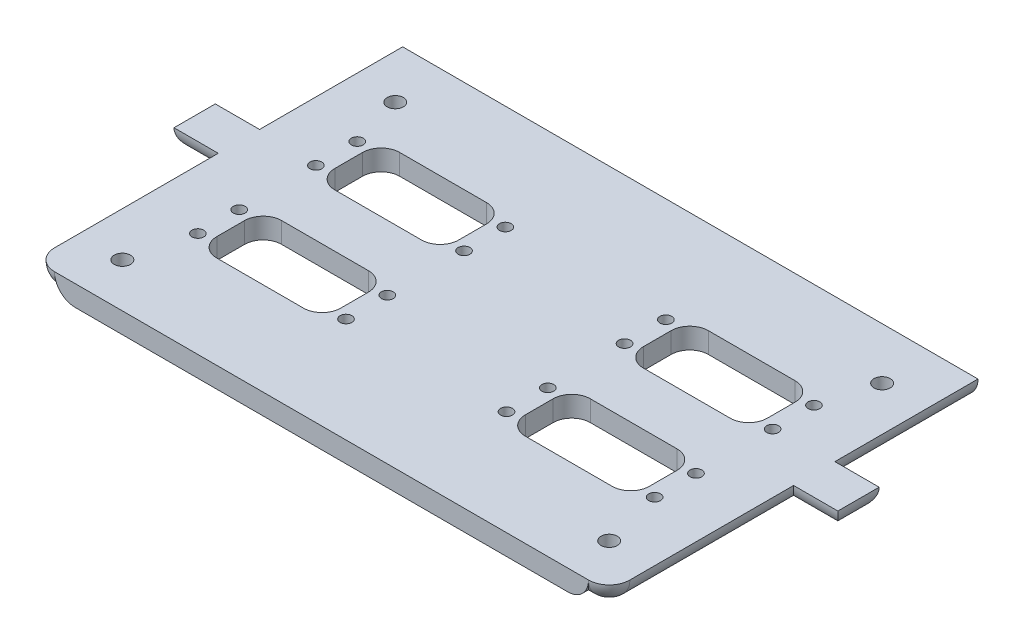
SolidWorks part; units mm, degrees
ref_plane "Front Plane" through (0, 0, 0) normal (0, 0, 1) x (1, 0, 0)
ref_plane "Top Plane" through (0, 0, 0) normal (0, 1, 0) x (1, 0, 0)
ref_plane "Right Plane" through (0, 0, 0) normal (1, 0, 0) x (0, 0, -1)
sketch "Sketch2" plane through (0, 0, 0) normal (0, 1, 0) x (1, 0, 0)
  line L1 (-97.5, 0) -> (97.5, 0)
  line L2 (-97.5, 0) -> (-97.5, -125)
  line L3 (-97.5, -125) -> (97.5, -125)
  line L4 (97.5, 0) -> (97.5, -125)
  point P4 (0, 0)
  dimension "D1" = 195
  dimension "D2" = 125
extrude "Boss-Extrude1" add sketch "Sketch2" along normal blind 57
sketch "Sketch3" plane through (0, 57, 0) normal (0, 1, 0) x (1, 0, 0)
  line L0 (97.5, 0) -> (-97.5, 0) construction
  line L1 (-90.5, 0) -> (90.5, 0)
  line L2 (-90.5, 0) -> (-90.5, -118)
  line L3 (-90.5, -118) -> (90.5, -118)
  line L4 (90.5, 0) -> (90.5, -118)
  line L5 (-97.5, 0) -> (-97.5, -125) construction
  line L6 (97.5, -125) -> (97.5, 0) construction
  line L7 (-97.5, -125) -> (97.5, -125) construction
  dimension "D1" = 7
  dimension "D2" = 7
  dimension "D3" = 7
extrude "Cut-Extrude1" cut sketch "Sketch3" against normal offset from surface (50 mm away) 7 up to face at (0, 0, 62.5)
sketch "Sketch5" plane through (-97.5, 0, 0) normal (-1, 0, 0) x (0, 0, 1)
  line L0 (48.5, 7) -> (48.5, 0)
  line L2 (48.5, 0) -> (62.5, 0)
  line L3 (0, 0) -> (125, 0) construction
  line L4 (62.5, 0) -> (62.5, 57)
  line L5 (0, 57) -> (125, 57) construction
  line L6 (62.5, 57) -> (55.5, 57)
  line L7 (55.5, 57) -> (55.5, 7)
  line L8 (55.5, 7) -> (48.5, 7)
  dimension "D1" = 7
  dimension "D2" = 7
  dimension "D3" = 7
  dimension "D4" = 55.5
extrude "Boss-Extrude2" add sketch "Sketch5" along normal blind 15
sketch "Sketch7" plane through (0, 0, 0) normal (0, -1, 0) x (1, 0, 0)
  line L0 (-97.5, 0) -> (-97.5, 48.5) construction
  line L1 (97.5, 0) -> (-97.5, 0) construction
  line L3 (-97.5, 125) -> (97.5, 125) construction
  circle A0 centre (-82.5, 17.5) radius 2.75
  circle A2 centre (-82.5, 110) radius 2.75
  dimension "D1" = 5.5
  dimension "D4" = 15
  dimension "D2" = 15
  dimension "D3" = 17.5
extrude "Cut-Extrude4" cut sketch "Sketch7" against normal up to next
sketch "Sketch34" plane through (0, 0, 0) normal (0, -1, 0) x (1, 0, 0)
  line L0 (-73.3, 63.75) -> (-51.3, 63.75) construction
  line L1 (-73.3, 42.75) -> (-51.3, 42.75)
  line L2 (-73.3, 42.75) -> (-73.3, 84.75)
  line L3 (-73.3, 84.75) -> (-51.3, 84.75)
  line L4 (-51.3, 42.75) -> (-51.3, 84.75)
  line L5 (-97.5, 0) -> (-97.5, 48.5) construction
  line L6 (-82.5, 17.5) -> (-82.5, 110) construction
  line L7 (-62.3, 42.75) -> (-62.3, 84.75) construction
  circle A0 centre (-57.3, 88.85) radius 2
  circle A1 centre (-67.3, 88.85) radius 2
  circle A2 centre (-78.45, 63.75) radius 2
  circle A3 centre (-46.15, 63.75) radius 2
  circle A4 centre (-57.3, 38.65) radius 2
  circle A5 centre (-67.3, 38.65) radius 2
  point P8 (-82.5, 63.75)
  point P9 (-73.3, 63.75)
  dimension "D4" = 4
  dimension "D5" = 10
  dimension "D1" = 22
  dimension "D2" = 42
  dimension "D3" = 24.2
  dimension "D6" = 25.1
  dimension "D7" = 25.1
  dimension "D8" = 5
  dimension "D9" = 5
  dimension "D10" = 16.15
  dimension "D11" = 16.15
extrude "Cut-Extrude8" cut sketch "Sketch34" against normal up to surface (7 mm away) up to face at (-82.5, 7, 20.25)
mirror "Mirror1" about plane through (0, 0, 0) normal (1, 0, 0) of "Cut-Extrude4", "Boss-Extrude2", "Cut-Extrude8"
mirror "Mirror2" about plane through (0, 0, 0) normal (0, 0, 1) of "Cut-Extrude4", "Cut-Extrude1", "Boss-Extrude1", "Mirror1", "Boss-Extrude2", "Cut-Extrude8"
fillet "Fillet2" radius 7 4 edges at (97.5, 28.5, -125) (-97.5, 28.5, -125) (-97.5, 28.5, 125) (97.5, 28.5, 125)
fillet "Fillet7" radius 7 32 edges at (97.5, 0, 0) (112.5, 0, 55.5) (105, 0, 62.5) (112.5, 3.5, 48.5) (105, 0, 48.5) (97.5, 3.5, 48.5) (-97.5, 0, 0) (-112.5, 0, -55.5) (-105, 0, -62.5) (-112.5, 3.5, -48.5) (-105, 0, -48.5) (-97.5, 3.5, -48.5) (97.5, 0, -90.25) (97.5, 3.5, -48.5) (105, 0, -48.5) (105, 0, -62.5) (112.5, 3.5, -48.5) (112.5, 0, -55.5) (-97.5, 0, 90.25) (-97.5, 3.5, 48.5) (-105, 0, 48.5) (-105, 0, 62.5) (97.5, 0, 90.25) (-97.5, 0, -90.25) (0, 0, -125) (0, 0, 125) (-95.4497, 0, 122.9497) (-95.4497, 0, -122.9497) (95.4497, 0, -122.9497) (-112.5, 3.5, 48.5) (95.4497, 0, 122.9497) (-112.5, 0, 55.5)
sketch "Sketch26" plane through (0, 0, 125) normal (0, 0, 1) x (1, 0, 0)
  line L0 (90.5, 0) -> (-90.5, 0) construction
  line L1 (-90.5, 7) -> (90.5, 7)
  line L2 (83.5, 0) -> (-83.5, 0)
  line L3 (-97.5, 7) -> (-97.5, 57) construction
  line L4 (97.5, 57) -> (97.5, 7) construction
  arc A0 (-90.5, 7) -> (-83.5, 0) centre (-83.5, 7) ccw
  arc A1 (83.5, 0) -> (90.5, 7) centre (83.5, 7) ccw
  dimension "D1" = 7
  dimension "D2" = 7
  dimension "D3" = 7
  dimension "D4" = 7
extrude "Boss-Extrude8" add sketch "Sketch26" against normal up to surface up to face at (0, 2.7751, 122.2249)
sketch "Sketch27" plane through (0, 0, -125) normal (0, 0, -1) x (-1, 0, 0)
  line L0 (90.5, 0) -> (-90.5, 0) construction
  line L1 (-90.5, 7) -> (90.5, 7)
  line L2 (-83.5, 0) -> (83.5, 0)
  line L3 (-97.5, 7) -> (-97.5, 57) construction
  line L5 (97.5, 57) -> (97.5, 7) construction
  arc A0 (-90.5, 7) -> (-83.5, 0) centre (-83.5, 7) ccw
  arc A1 (83.5, 0) -> (90.5, 7) centre (83.5, 7) ccw
  dimension "D1" = 7
  dimension "D3" = 7
  dimension "D4" = 7
  dimension "D2" = 7
extrude "Boss-Extrude9" add sketch "Sketch27" against normal up to next
sketch "Sketch29" plane through (0, 57, 0) normal (0, 1, 0) x (1, 0, 0)
  line L1 (-228.61, 228.4159) -> (231.715, 228.4159)
  line L2 (-228.61, 228.4159) -> (-228.61, -215.9957)
  line L3 (-228.61, -215.9957) -> (231.715, -215.9957)
  line L4 (231.715, 228.4159) -> (231.715, -215.9957)
extrude "Cut-Extrude5" cut sketch "Sketch29" against normal up to surface (50 mm away) up to face at (-57.3, 7, -36.65)
sketch "Sketch30" plane through (0, 7, 0) normal (0, 1, 0) x (1, 0, 0)
  line L0 (-97.5, 0) -> (97.5, 0) construction
  line L1 (97.5, -48.5) -> (97.5, 48.5) construction
  circle A0 centre (0, 64) radius 48
  point P6 (0, 0)
  dimension "D1" = 64
  dimension "D3" = 96
  dimension "D2" = 64
extrude "Boss-Extrude10" add sketch "Sketch30" along normal blind 11
sketch "Sketch31" plane through (0, 0, 0) normal (0, -1, 0) x (1, 0, 0)
  circle A0 centre (0, -64) radius 41
  circle A1 centre (0, -64) radius 48 construction
  dimension "D1" = 82
extrude "Cut-Extrude6" cut sketch "Sketch31" against normal blind 11
sketch "Sketch32" plane through (0, 11, 0) normal (0, -1, 0) x (1, 0, 0)
  line L0 (0, -98) -> (0, -30) construction
  line L1 (-34, -64) -> (34, -64) construction
  circle A0 centre (0, -30) radius 3.2
  circle A1 centre (0, -98) radius 3.2
  circle A2 centre (34, -64) radius 3.2
  circle A3 centre (-34, -64) radius 3.2
  point P8 (0, -64)
  point P10 (0, -64)
  dimension "D1" = 6.4
  dimension "D2" = 30
  dimension "D3" = 68
  dimension "D4" = 68
extrude "Cut-Extrude7" cut sketch "Sketch32" against normal up to surface (7 mm away) up to face at (0, 18, -16)
fillet "Fillet8" radius 7 1 edges at (0, 18, -16)
fillet "Fillet11" radius 6.3 8 edges at (51.3, 3.5, 42.75) (73.3, 3.5, 84.75) (51.3, 3.5, 84.75) (73.3, 3.5, 42.75) (-51.3, 3.5, 42.75) (-73.3, 3.5, 42.75) (-51.3, 3.5, 84.75) (-73.3, 3.5, 84.75)
sketch "Sketch37" plane through (0, 0, 0) normal (0, -1, 0) x (1, 0, 0)
  line L0 (-90.5, -55.5) -> (-90.5, -118) construction
  line L1 (43.5, -100) -> (85.5, -100)
  line L2 (43.5, -100) -> (43.5, -25)
  line L3 (43.5, -25) -> (85.5, -25)
  line L4 (85.5, -100) -> (85.5, -25)
  line L5 (-85.5, -100) -> (-43.5, -100)
  line L6 (-85.5, -100) -> (-85.5, -25)
  line L7 (-85.5, -25) -> (-43.5, -25)
  line L8 (-43.5, -100) -> (-43.5, -25)
  line L9 (90.5, -118) -> (90.5, -55.5) construction
  line L10 (83.5, -125) -> (-83.5, -125) construction
  dimension "D1" = 5
  dimension "D2" = 5
  dimension "D3" = 25
  dimension "D4" = 25
  dimension "D5" = 75
  dimension "D6" = 42
  dimension "D7" = 42
  dimension "D8" = 75
extrude "Boss-Extrude11" add sketch "Sketch37" against normal up to surface (7 mm away)
ref_plane "Plane1" through (0, 0, 0) normal (0, 0, 1) x (1, 0, 0)
sketch "Sketch39" plane through (0, 0, -125) normal (0, 0, -1) x (-1, 0, 0)
  line L1 (-129.8228, 54.0193) -> (124.9489, 54.0193)
  line L2 (-129.8228, 54.0193) -> (-129.8228, -42.794)
  line L3 (-129.8228, -42.794) -> (124.9489, -42.794)
  line L4 (124.9489, 54.0193) -> (124.9489, -42.794)
extrude "Cut-Extrude9" cut sketch "Sketch39" against normal up to surface (125 mm away)
sketch "Sketch40" plane through (0, 0, 0) normal (0, -1, 0) x (1, 0, 0)
  line L1 (-83.2993, 28.1612) -> (-39.8773, 28.1612)
  line L2 (-83.2993, 28.1612) -> (-83.2993, 97.725)
  line L3 (-83.2993, 97.725) -> (-39.8773, 97.725)
  line L4 (-39.8773, 28.1612) -> (-39.8773, 97.725)
extrude "Boss-Extrude12" add sketch "Sketch40" against normal up to surface (7 mm away) up to face at (0, 7, 66.6357)
sketch "Sketch41" plane through (0, 0, 0) normal (0, -1, 0) x (1, 0, 0)
  line L1 (-67, 93.5) -> (-37.6, 93.5)
  line L2 (-73.3, 87.2) -> (-73.3, 77.8)
  line L3 (-67, 71.5) -> (-37.6, 71.5)
  line L4 (-31.3, 87.2) -> (-31.3, 77.8)
  line L6 (-83.5, 125) -> (83.5, 125) construction
  line L7 (-67, 53.5) -> (-37.6, 53.5)
  line L8 (-73.3, 47.2) -> (-73.3, 37.8)
  line L9 (-67, 31.5) -> (-37.6, 31.5)
  line L10 (-31.3, 47.2) -> (-31.3, 37.8)
  line L11 (-97.5, 62.5) -> (-97.5, 118) construction
  arc A0 (-37.6, 93.5) -> (-31.3, 87.2) centre (-37.6, 87.2) cw
  arc A1 (-37.6, 71.5) -> (-31.3, 77.8) centre (-37.6, 77.8) ccw
  arc A2 (-73.3, 77.8) -> (-67, 71.5) centre (-67, 77.8) ccw
  arc A3 (-67, 93.5) -> (-73.3, 87.2) centre (-67, 87.2) ccw
  circle A5 centre (-27.2, 89.5) radius 2
  circle A6 centre (-27.2, 75.5) radius 2
  circle A8 centre (-77.4, 75.5) radius 2
  circle A9 centre (-77.4, 89.5) radius 2
  arc A10 (-37.6, 53.5) -> (-31.3, 47.2) centre (-37.6, 47.2) cw
  arc A11 (-37.6, 31.5) -> (-31.3, 37.8) centre (-37.6, 37.8) ccw
  arc A12 (-73.3, 37.8) -> (-67, 31.5) centre (-67, 37.8) ccw
  arc A13 (-67, 53.5) -> (-73.3, 47.2) centre (-67, 47.2) ccw
  circle A15 centre (-27.2, 49.5) radius 2
  circle A16 centre (-27.2, 35.5) radius 2
  circle A18 centre (-77.4, 35.5) radius 2
  circle A19 centre (-77.4, 49.5) radius 2
  point P28 (-52.3, 71.5)
  dimension "D4" = 6.3
  dimension "D6" = 4
  dimension "D15" = 6.3
  dimension "D2" = 22
  dimension "D3" = 42
  dimension "D5" = 31.5
  dimension "D9" = 4
  dimension "D10" = 4
  dimension "D11" = 4.1
  dimension "D12" = 4.1
  dimension "D13" = 22
  dimension "D14" = 42
  dimension "D18" = 4
  dimension "D19" = 4
  dimension "D20" = 4.1
  dimension "D21" = 4.1
  dimension "D22" = 18
  dimension "D23" = 24.2
extrude "Cut-Extrude10" cut sketch "Sketch41" against normal up to surface (7 mm away) up to face at (0, 7, 66.6357)
ref_plane "Plane3" through (0, 0, 0) normal (1, 0, 0) x (0, 0, -1)
mirror "Mirror3" about plane through (0, 0, 0) normal (1, 0, 0) of "Boss-Extrude12"
mirror "Mirror4" about plane through (0, 0, 0) normal (1, 0, 0) of "Cut-Extrude10"
